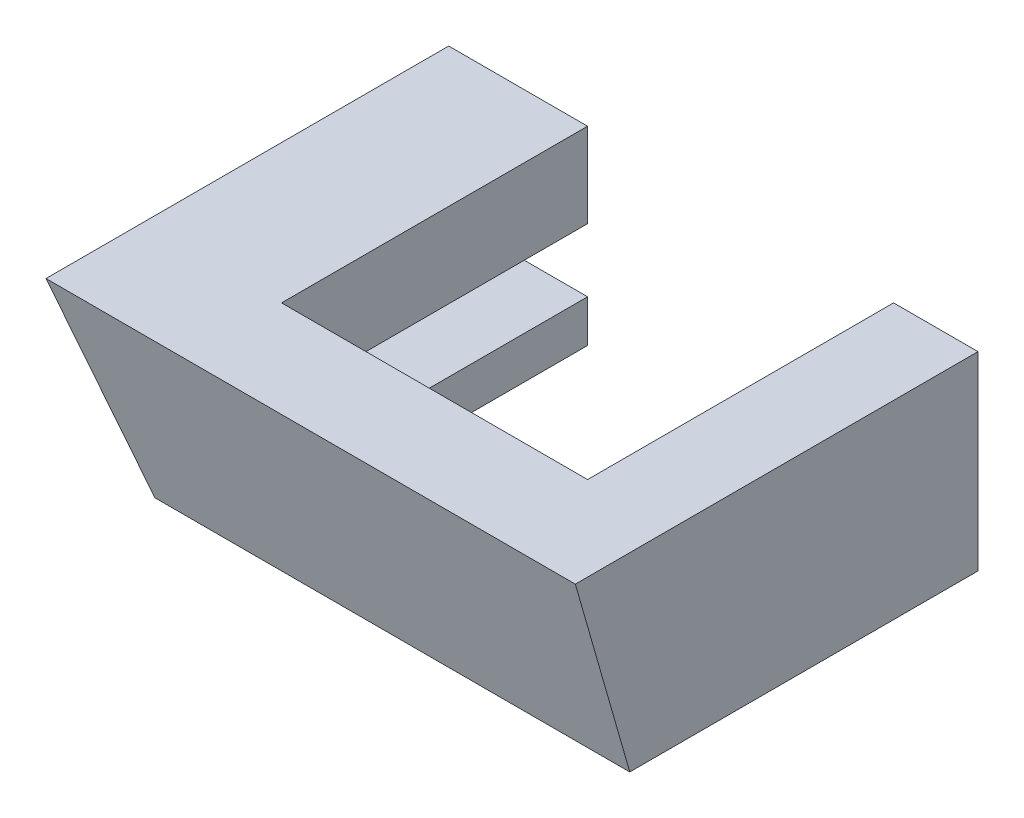
SolidWorks part; units mm, degrees
ref_plane "Front Plane" through (0, 0, 0) normal (0, 0, 1) x (1, 0, 0)
ref_plane "Top Plane" through (0, 0, 0) normal (0, 1, 0) x (1, 0, 0)
ref_plane "Right Plane" through (0, 0, 0) normal (1, 0, 0) x (0, 0, -1)
sketch "Sketch1" plane through (0, 0, 0) normal (0, 1, 0) x (1, 0, 0)
  line L4 (-45.0893, -57.125) -> (-22.5893, -57.125)
  line L5 (-22.5893, -57.125) -> (-22.5893, -40.625)
  line L6 (-22.5893, -40.625) -> (-45.0893, -40.625)
  line L7 (-45.0893, -40.625) -> (-45.0893, -57.125)
  dimension "D1" = 16.5
  dimension "D2" = 22.5
extrude "Boss-Extrude1" add sketch "Sketch1" along normal blind 9
sketch "Sketch3" plane through (0, 0, 0) normal (0, -1, 0) x (1, 0, 0)
  line L0 (-41.0893, 55.125) -> (-41.0893, 40.625)
  line L1 (-22.5893, 40.625) -> (-45.0893, 40.625) construction
  line L2 (-41.0893, 40.625) -> (-26.5893, 40.625)
  line L3 (-26.5893, 40.625) -> (-26.5893, 55.125)
  line L4 (-26.5893, 55.125) -> (-41.0893, 55.125)
  line L6 (-45.0893, 57.125) -> (-22.5893, 57.125) construction
  point P11 (-33.8393, 57.125)
  point P12 (-33.8393, 55.125)
  dimension "D1" = 2
  dimension "D2" = 14.5
extrude "Cut-Extrude2" cut sketch "Sketch3" against normal through all
draft "Draft1" type of draft neutral plane draft angle 16 faces to draft 1 face at (-45.0893, 4.5, 48.875) neutral plane through (0, 0, 0) neutral plane normal (0, -1, 0) parameters "D1"=16
draft "Draft3" type of draft neutral plane draft angle 16 faces to draft 1 face at (-34.4845, 4.5, 57.125) neutral plane through (0, 0, 0) neutral plane normal (0, -1, 0) parameters "D1"=16
sketch "Sketch9" plane through (0, 0, 40.625) normal (0, 0, 1) x (-1, 0, 0)
  line L0 (26.5893, -9) -> (26.5893, 0) construction
  line L1 (23.5893, -2) -> (26.5893, -2)
  line L2 (23.5893, -2) -> (23.5893, -5)
  line L3 (23.5893, -5) -> (26.5893, -5)
  line L4 (26.5893, -2) -> (26.5893, -5)
  line L5 (23.5893, -2) -> (26.5893, -5) construction
  line L6 (23.5893, -5) -> (26.5893, -2) construction
  line L7 (22.5893, -9) -> (26.5893, -9) construction
  line L8 (33.8393, -9) -> (33.8393, 0) construction
  line L10 (26.5893, 0) -> (41.0893, 0) construction
  line L11 (44.0893, -5) -> (41.0893, -2) construction
  line L12 (44.0893, -2) -> (41.0893, -5) construction
  line L13 (41.0893, -2) -> (41.0893, -5)
  line L14 (44.0893, -5) -> (41.0893, -5)
  line L15 (44.0893, -2) -> (44.0893, -5)
  line L16 (44.0893, -2) -> (41.0893, -2)
  line L18 (47.67, -9) -> (22.5893, -9) construction
  point P0 (25.0893, -3.5)
  point P21 (42.5893, -3.5)
  dimension "D1" = 3
  dimension "D2" = 3
  dimension "D3" = 4
extrude "Cut-Extrude3" cut sketch "Sketch9" along normal up to surface (14.5 mm away) up to face at (-33.8393, 4.5, 55.125)
